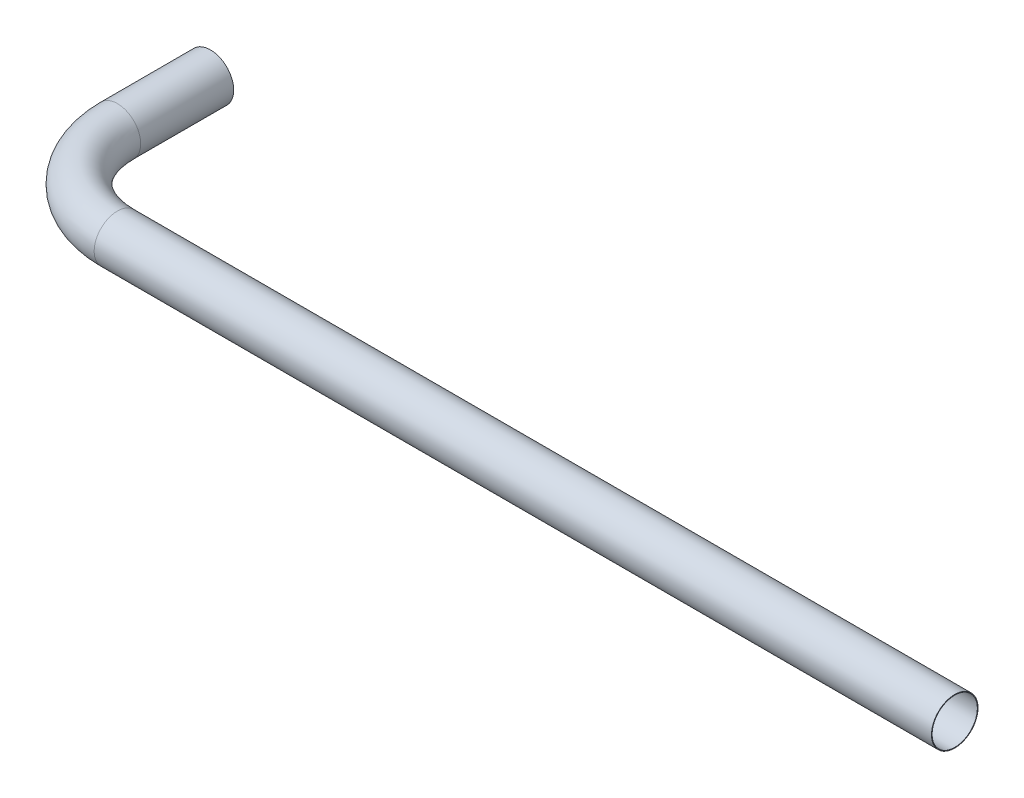
SolidWorks part; units mm, degrees
ref_plane "Front Plane" through (0, 0, 0) normal (0, 0, 1) x (1, 0, 0)
ref_plane "Top Plane" through (0, 0, 0) normal (0, 1, 0) x (1, 0, 0)
ref_plane "Right Plane" through (0, 0, 0) normal (1, 0, 0) x (0, 0, -1)
sketch "Sketch1" plane through (0, 0, 0) normal (0, 0, 1) x (1, 0, 0)
  circle A0 centre (0, 0) radius 3.0861
  circle A1 centre (0, 0) radius 3.175
  dimension "D1" = 6.1722
  dimension "D2" = 6.35
sketch3d "3DSketch1"
  line L0 (0, 0, 0) -> (0, 0, 12.7)
  line L1 (12.7, 0, 25.4) -> (127, 0, 25.4)
  arc A0 (0, 0, 12.7) -> (12.7, 0, 25.4) centre (12.7, 0, 12.7) ccw
  point P6 (0, 0, 25.4)
  point P7 (12.7, 12.7, 12.7)
  dimension "D1" = 12.7
  dimension "D2" = 25.4
  dimension "D3" = 127
sweep "Sweep1" add profiles "Sketch1" path "3DSketch1"
